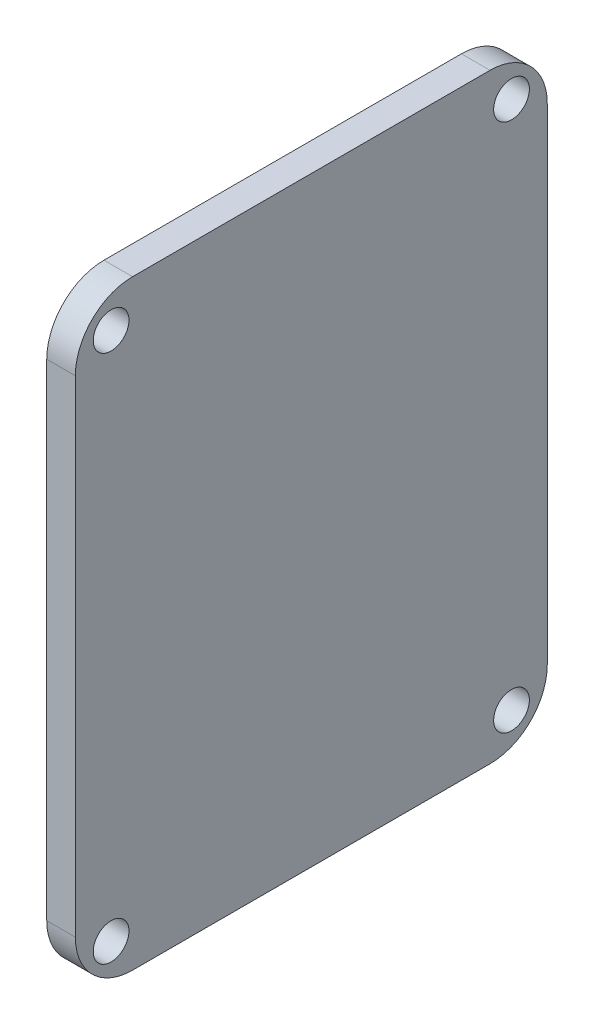
SolidWorks part; units mm, degrees
ref_plane "Front Plane" through (0, 0, 0) normal (1, 0, 0) x (0, 1, 0)
ref_plane "Top Plane" through (0, 0, 0) normal (0, 0, 1) x (0, 1, 0)
ref_plane "Right Plane" through (0, 0, 0) normal (0, 1, 0) x (-1, 0, 0)
sketch "Sketch2" plane through (0, 0, 0) normal (1, 0, 0) x (0, 1, 0)
  line L0 (-18.5, 14) -> (-18.5, -14) construction
  line L1 (-17, -16.5) -> (17, -16.5)
  line L2 (-21, -12.5) -> (-21, 12.5)
  line L3 (-17, 16.5) -> (17, 16.5)
  line L4 (21, -12.5) -> (21, 12.5)
  line L5 (0, 16.5) -> (0, -16.5) construction
  line L6 (-21, 0) -> (21, 0) construction
  line L7 (-18.5, 14) -> (18.5, 14) construction
  line L8 (18.5, 14) -> (18.5, -14) construction
  line L9 (18.5, -14) -> (-18.5, -14) construction
  circle A0 centre (-18.5, 14) radius 1.25
  circle A1 centre (-18.5, -14) radius 1.25
  circle A2 centre (18.5, 14) radius 1.25
  circle A3 centre (18.5, -14) radius 1.25
  arc A4 (-17, -16.5) -> (-21, -12.5) centre (-17, -12.5) cw
  arc A5 (17, -16.5) -> (21, -12.5) centre (17, -12.5) ccw
  arc A6 (17, 16.5) -> (21, 12.5) centre (17, 12.5) cw
  arc A7 (-21, 12.5) -> (-17, 16.5) centre (-17, 12.5) cw
  point P0 (0, 0)
  point P19 (-21, -16.5)
  point P22 (21, -16.5)
  point P25 (21, 16.5)
  dimension "D1" = 2.5
  dimension "D5" = 37
  dimension "D6" = 4
  dimension "D2" = 33
  dimension "D3" = 42
  dimension "D4" = 28
extrude "Boss-Extrude1" add sketch "Sketch2" along normal blind 2
